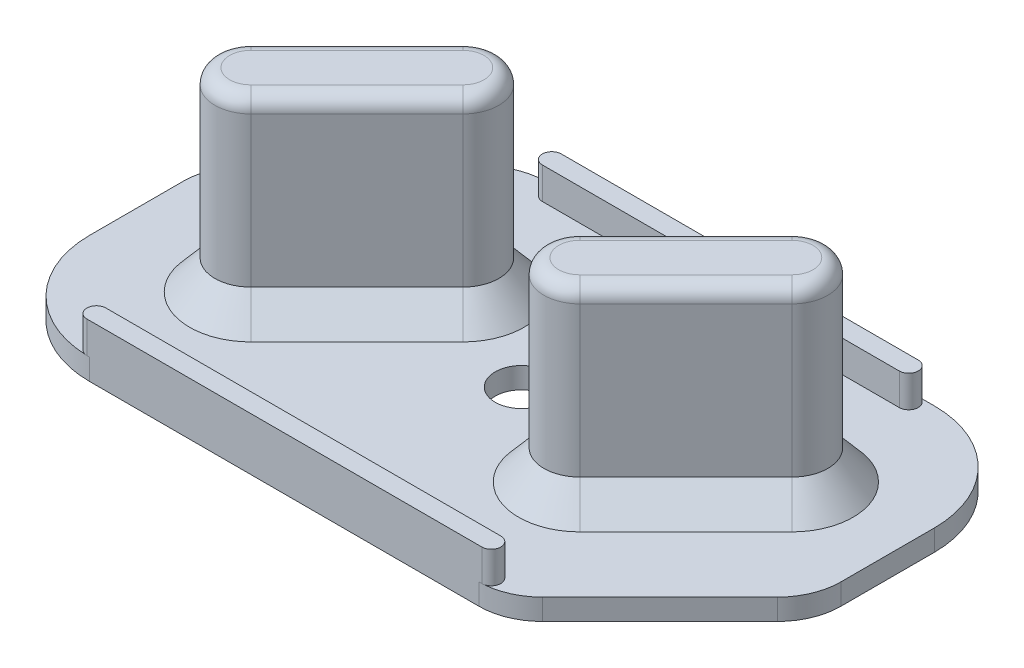
SolidWorks part; units mm, degrees
material "Caoutchouc silicone"
ref_plane "Plan de face" through (0, 0, 0) normal (0, 0, 1) x (1, 0, 0)
ref_plane "Plan de dessus" through (0, 0, 0) normal (0, 1, 0) x (1, 0, 0)
ref_plane "Plan de droite" through (0, 0, 0) normal (1, 0, 0) x (0, 0, -1)
sketch "Esquisse1" plane through (0, 0, 0) normal (0, 1, 0) x (1, 0, 0)
  line L0 (-11, -9) -> (7.435, -9)
  line L1 (9.5563, -8.1213) -> (15.1213, -2.5563)
  line L2 (16, -0.435) -> (16, 4)
  line L3 (11, 9) -> (-7.435, 9)
  line L4 (-9.5563, 8.1213) -> (-15.1213, 2.5563)
  line L5 (-16, 0.435) -> (-16, -4)
  line L6 (-16, 0) -> (16, 0) construction
  arc A0 (7.435, -9) -> (9.5563, -8.1213) centre (7.435, -6) ccw
  arc A1 (15.1213, -2.5563) -> (16, -0.435) centre (13, -0.435) ccw
  arc A2 (16, 4) -> (11, 9) centre (11, 4) ccw
  arc A3 (-7.435, 9) -> (-9.5563, 8.1213) centre (-7.435, 6) ccw
  arc A4 (-15.1213, 2.5563) -> (-16, 0.435) centre (-13, 0.435) ccw
  arc A5 (-16, -4) -> (-11, -9) centre (-11, -4) ccw
  circle A7 centre (0.45, 0) radius 1.25
  point P22 (0, 0)
  point P23 (1.7, 0)
  dimension "D7" = 2.5
  dimension "D8" = 14.3
  dimension "D4" = 3
  dimension "D1" = 18
  dimension "D2" = 32
  dimension "D3" = 25
  dimension "D5" = 5
  dimension "D6" = 9
  dimension "D9" = 135
extrude "Boss.-Extru.1" add sketch "Esquisse1" along normal blind 1
sketch "Esquisse2" plane through (0, 1, 0) normal (0, 1, 0) x (1, 0, 0)
  line L0 (-9.8605, -2.5102) -> (-4.84, 2.5102) construction
  line L1 (-11.0625, -1.3081) -> (-6.0421, 3.7123)
  line L2 (-8.6584, -3.7123) -> (-3.6379, 1.3081)
  line L3 (5.7191, -2.5102) -> (10.7395, 2.5102) construction
  line L4 (4.517, -1.3081) -> (9.5375, 3.7123)
  line L5 (6.9212, -3.7123) -> (11.9416, 1.3081)
  line L6 (-11, -9) -> (7.435, -9) construction
  line L8 (-9.8605, -4.2102) -> (-9.8605, 4.2102) construction
  line L9 (-9.8605, 4.2102) -> (-4.84, 4.2102) construction
  arc A0 (-11.0625, -1.3081) -> (-8.6584, -3.7123) centre (-9.8605, -2.5102) ccw
  arc A1 (-3.6379, 1.3081) -> (-6.0421, 3.7123) centre (-4.84, 2.5102) ccw
  arc A2 (4.517, -1.3081) -> (6.9212, -3.7123) centre (5.7191, -2.5102) ccw
  arc A3 (11.9416, 1.3081) -> (9.5375, 3.7123) centre (10.7395, 2.5102) ccw
  point P2 (-7.3502, 0)
  point P7 (8.2293, 0)
  point P14 (12.4395, 2.5102)
  point P15 (-11.5605, -2.5102)
  point P16 (-11.0625, -3.7123)
  point P17 (-3.6379, 3.7123)
  point P18 (-3.14, 2.5102)
  point P19 (4.0191, -2.5102)
  point P20 (5.7191, -4.2102)
  point P22 (-4.84, 4.2102)
  point P24 (0.45, 0)
  point P25 (-9.8605, 0)
  dimension "D1" = 24
  dimension "D2" = 10.5
  dimension "D3" = 135
  dimension "D4" = 3.4
  dimension "D5" = 3.59
extrude "Boss.-Extru.2" add sketch "Esquisse2" along normal blind 9.2
fillet "Congé1" radius 0.7 8 edges at (-8.5523, 10.2, -1.2021) (-3.6379, 10.2, -3.7123) (-6.1481, 10.2, 1.2021) (-11.0625, 10.2, 3.7123) (4.517, 10.2, 3.7123) (9.4314, 10.2, 1.2021) (11.9416, 10.2, -3.7123) (7.0272, 10.2, -1.2021)
sketch "Esquisse3" plane through (0, 1, 0) normal (0, 1, 0) x (1, 0, 0)
  line L0 (-9.8605, -2.5102) -> (-4.84, 2.5102) construction
  line L1 (-11.9111, -0.4596) -> (-6.8906, 4.5608)
  line L2 (-7.8098, -4.5608) -> (-2.7894, 0.4596)
  line L3 (5.7191, -2.5102) -> (10.7395, 2.5102) construction
  line L4 (3.6685, -0.4596) -> (8.6889, 4.5608)
  line L5 (7.7697, -4.5608) -> (12.7902, 0.4596)
  line L7 (-6.0421, 3.7123) -> (-11.0625, -1.3081) construction
  line L9 (-8.6584, -3.7123) -> (-3.6379, 1.3081) construction
  line L10 (-11, -9) -> (7.435, -9) construction
  line L11 (9.5375, 3.7123) -> (4.517, -1.3081) construction
  arc A0 (-11.9111, -0.4596) -> (-7.8098, -4.5608) centre (-9.8605, -2.5102) ccw
  arc A1 (-2.7894, 0.4596) -> (-6.8906, 4.5608) centre (-4.84, 2.5102) ccw
  arc A2 (3.6685, -0.4596) -> (7.7697, -4.5608) centre (5.7191, -2.5102) ccw
  arc A3 (12.7902, 0.4596) -> (8.6889, 4.5608) centre (10.7395, 2.5102) ccw
  arc A4 (-11.0625, -1.3081) -> (-8.6584, -3.7123) centre (-9.8605, -2.5102) ccw construction
  arc A5 (-3.6379, 1.3081) -> (-6.0421, 3.7123) centre (-4.84, 2.5102) ccw construction
  point P2 (-7.3502, 0)
  point P7 (8.2293, 0)
  point P20 (-11.0625, -3.7123)
  point P21 (-11.9111, -4.5608)
  point P25 (-3.6379, 3.7123)
  point P26 (-2.7894, 4.5608)
  dimension "D1" = 45
  dimension "D2" = 1.2
  dimension "D3" = 1.2
  dimension "D4" = 1.2
  dimension "D5" = 1.2
  dimension "D6" = 1.2
extrude "Boss.-Extru.3" add sketch "Esquisse3" along normal blind 1.4
chamfer "Chanfrein1" distance 1.4 distance2 1.2 8 edges at (12.7902, 2.4, -4.5608) (6.1787, 2.4, -2.0506) (3.6685, 2.4, 4.5608) (10.2799, 2.4, 2.0506) (-2.7894, 2.4, -4.5608) (-9.4008, 2.4, -2.0506) (-11.9111, 2.4, 4.5608) (-5.2996, 2.4, 2.0506) first distance on face at (11.7648, 1.7, -3.5355) first distance on face at (6.1787, 1.7, -2.0506) first distance on face at (4.6938, 1.7, 3.5355) first distance on face at (10.2799, 1.7, 2.0506) first distance on face at (-3.8147, 1.7, -3.5355) first distance on face at (-9.4008, 1.7, -2.0506) first distance on face at (-10.8858, 1.7, 3.5355) first distance on face at (-5.2996, 1.7, 2.0506)
sketch "Esquisse4" plane through (0, 1, 0) normal (0, 1, 0) x (1, 0, 0)
  line L0 (-6.6675, 8.55) -> (10.2325, 8.55) construction
  line L1 (-6.6675, 9) -> (10.2325, 9)
  line L2 (-6.6675, 8.1) -> (10.2325, 8.1)
  line L3 (11, 9) -> (-7.435, 9) construction
  line L6 (-11.1325, -8.55) -> (7.5675, -8.55) construction
  line L7 (-11.1325, -8.1) -> (7.5675, -8.1)
  line L8 (-11.1325, -9) -> (7.5675, -9)
  line L9 (-11, -9) -> (7.435, -9) construction
  arc A0 (-6.6675, 9) -> (-6.6675, 8.1) centre (-6.6675, 8.55) ccw
  arc A1 (10.2325, 8.1) -> (10.2325, 9) centre (10.2325, 8.55) ccw
  arc A2 (-11.1325, -8.1) -> (-11.1325, -9) centre (-11.1325, -8.55) ccw
  arc A3 (7.5675, -9) -> (7.5675, -8.1) centre (7.5675, -8.55) ccw
  point P2 (1.7825, 8.55)
  point P9 (-7.1175, 8.55)
  point P10 (10.6825, 8.55)
  point P11 (-1.7825, -8.55)
  point P14 (1.7825, 9)
  point P22 (-1.7825, -9)
  point P23 (-10.6825, -8.55)
  point P24 (7.1175, -8.55)
  dimension "D1" = 17.8
  dimension "D2" = 0.9
  dimension "D3" = 17.8
  dimension "D4" = 0.9
extrude "Boss.-Extru.4" add sketch "Esquisse4" along normal blind 1.5
sketch "Esquisse5" plane through (0, 10.2, 0) normal (0, 1, 0) x (1, 0, 0)
  line L0 (-5.5471, 3.2173) -> (-10.5676, -1.8031) construction
  line L1 (10.0324, 3.2173) -> (5.012, -1.8031) construction
  circle A0 centre (-7.3502, 0) radius 1
  circle A1 centre (8.2293, 0) radius 1
  point P0 (-7.3502, 0)
  point P6 (-8.3203, 0.4441)
